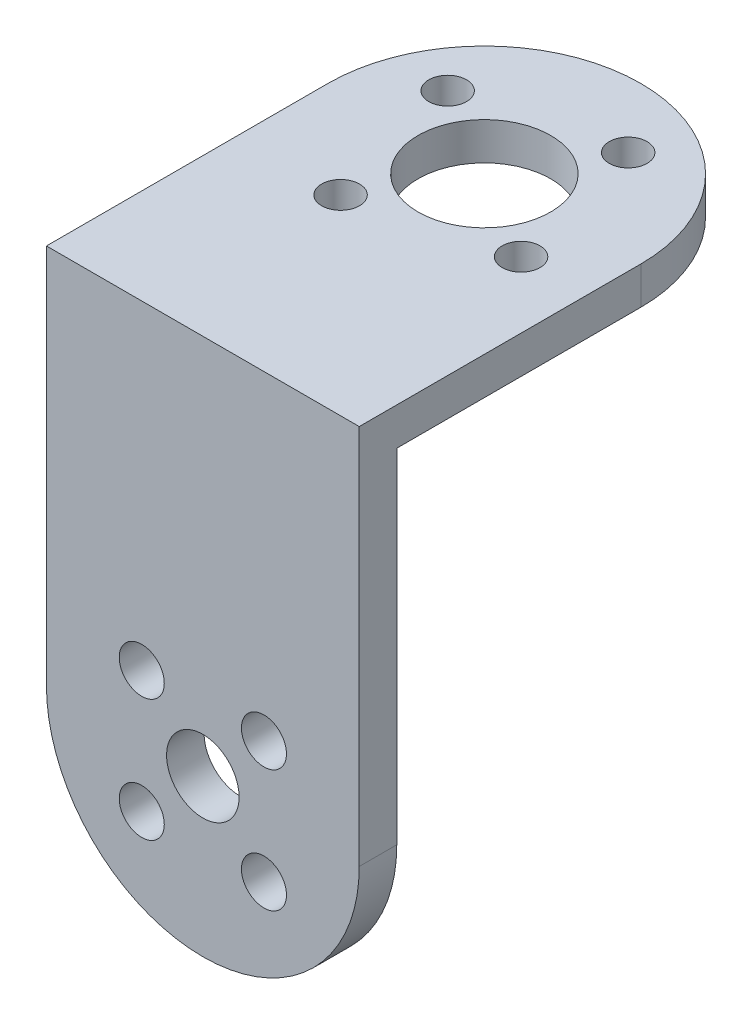
SolidWorks part; units mm, degrees
ref_plane "Alzado" through (0, 0, 0) normal (0, 0, 1) x (1, 0, 0)
ref_plane "Planta" through (0, 0, 0) normal (0, 1, 0) x (1, 0, 0)
ref_plane "Vista lateral" through (0, 0, 0) normal (1, 0, 0) x (0, 0, -1)
sketch "Croquis1" plane through (0, 0, 0) normal (0, 1, 0) x (1, 0, 0)
  line L0 (0, 22.25) -> (-23.245, 22.25) construction
  line L1 (-12.5, 9.75) -> (12.5, 9.75) construction
  line L2 (-12.5, 9.75) -> (-12.5, -9.75)
  line L3 (-12.5, -9.75) -> (12.5, -9.75)
  line L4 (12.5, 9.75) -> (12.5, -9.75)
  line L5 (-12.5, 9.75) -> (12.5, -9.75) construction
  line L6 (-12.5, -9.75) -> (12.5, 9.75) construction
  line L7 (-12.5, -9.75) -> (-23.245, -9.75) construction
  line L8 (0, 9.75) -> (6.3778, 20.5005) construction
  arc A0 (12.5, 9.75) -> (-12.5, 9.75) centre (0, 9.75) ccw
  circle A1 centre (0, 9.75) radius 5.3
  circle A2 centre (0, 9.75) radius 12.5 construction
  circle A3 centre (0, 9.75) radius 8.3867 construction
  circle A4 centre (4.2791, 16.9629) radius 1.5114
  circle A5 centre (7.2129, 5.4709) radius 1.5114
  circle A6 centre (-4.2791, 2.5371) radius 1.5114
  circle A7 centre (-7.2129, 14.0291) radius 1.5114
  point P0 (0, 0)
  point P25 (0, 9.75)
  dimension "D1" = 25
  dimension "D3" = 10.6
  dimension "D4" = 59.321
  dimension "D2" = 32
  dimension "D5" = 4
extrude "Saliente-Extruir1" add sketch "Croquis1" along normal blind 3
sketch "Croquis3" plane through (0, 0, 9.75) normal (0, 0, 1) x (1, 0, 0)
  line L1 (12.5, 3) -> (-12.5, 3)
  line L2 (12.5, 3) -> (12.5, -27.4481)
  line L3 (12.5, -27.4481) -> (-12.5, -27.4481) construction
  line L4 (-12.5, 3) -> (-12.5, -27.4481)
  line L5 (0, -27.4481) -> (-8.8388, -36.2869) construction
  arc A0 (-12.5, -27.4481) -> (12.5, -27.4481) centre (0, -27.4481) ccw
  circle A1 centre (0, -27.4481) radius 12.5 construction
  circle A2 centre (0, -27.4481) radius 6.9056 construction
  circle A3 centre (-4.883, -32.3311) radius 1.8
  circle A4 centre (-4.883, -22.565) radius 1.8
  circle A5 centre (4.883, -22.565) radius 1.8
  circle A6 centre (4.883, -32.3311) radius 1.8
  circle A7 centre (0, -27.4481) radius 2.8984
  point P21 (0, -27.4481)
  dimension "D2" = 3.6
  dimension "D1" = 45
  dimension "D3" = 4
extrude "Saliente-Extruir2" add sketch "Croquis3" along normal blind 3
